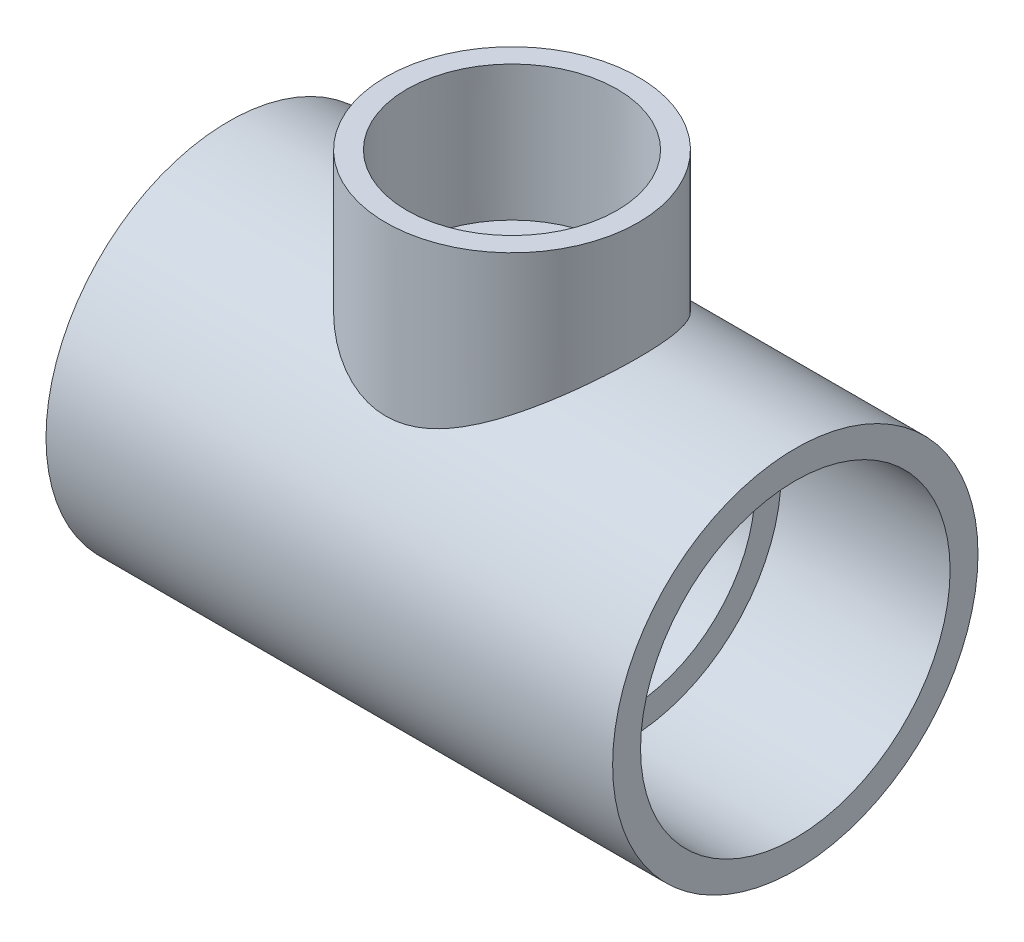
SolidWorks part; units mm, degrees
ref_plane "Front Plane" through (0, 0, 0) normal (0, 0, 1) x (1, 0, 0)
ref_plane "Top Plane" through (0, 0, 0) normal (0, 1, 0) x (1, 0, 0)
ref_plane "Right Plane" through (0, 0, 0) normal (1, 0, 0) x (0, 0, -1)
sketch "Sketch0" plane through (0, 0, 0) normal (0, 0, 1) x (1, 0, 0)
  line L0 (-81.7372, 0) -> (0, 0) construction
  line L1 (0, 0) -> (0, 86.4616) construction
  line L2 (-33.2994, 0) -> (0, 0) construction
  line L3 (0, 0) -> (0, 47.625) construction
  line L4 (-81.7372, 52.705) -> (-81.7372, -52.705) construction
  line L5 (-33.2994, 44.3484) -> (-81.7372, 44.6532) construction
  line L6 (-33.2994, 44.3484) -> (-33.2994, -44.3484) construction
  line L7 (-33.2994, -44.3484) -> (-81.7372, -44.6532) construction
  line L8 (-81.7372, 44.6532) -> (-81.7372, -44.6532) construction
  line L9 (-36.4109, 86.4616) -> (36.4109, 86.4616) construction
  line L10 (-30.3149, 86.4616) -> (30.3149, 86.4616) construction
  line L11 (30.3149, 86.4616) -> (30.0863, 47.625) construction
  line L12 (30.0863, 47.625) -> (-30.0863, 47.625) construction
  line L13 (-30.0863, 47.625) -> (-30.3149, 86.4616) construction
  line L14 (-33.2994, 36.83) -> (-33.2994, -36.83) construction
  line L15 (-81.7372, 0) -> (-33.2994, 0) construction
  line L16 (0, 86.4616) -> (0, 47.625) construction
  line L17 (0, 0) -> (33.2994, 0) construction
  line L18 (-24.6253, 47.625) -> (24.6253, 47.625) construction
  line L19 (33.2994, 0) -> (81.7372, 0) construction
  dimension "H" = 81.7372
  dimension "G" = 33.2994
  dimension "M" = 105.41
  dimension "OD A" = 89.3064
  dimension "OD B" = 88.6968
  dimension "ID" = 73.66
  dimension "H3" = 86.4616
  dimension "G3" = 47.625
  dimension "M3" = 72.8218
  dimension "OD A3" = 60.6298
  dimension "OD B3" = 60.1726
  dimension "ID3" = 49.2506
sketch "Sketch1" plane through (0, 0, 0) normal (0, 0, 1) x (1, 0, 0)
  line L0 (-81.7372, 0) -> (0, 0) construction
  line L1 (-81.7372, 0) -> (0, 0) construction
  line L2 (0, 0) -> (0, -52.705) construction
  line L3 (-81.7372, -52.705) -> (-33.2994, -52.705)
  line L4 (-81.7372, -52.705) -> (-81.7372, -44.6532)
  line L5 (-81.7372, -44.6532) -> (-33.2994, -44.3484)
  line L6 (-33.2994, -52.705) -> (-33.2994, -44.3484)
  line L7 (-33.2994, -52.705) -> (0, -52.705) construction
  line L8 (81.7372, -44.6532) -> (33.2994, -44.3484)
  line L9 (81.7372, -52.705) -> (81.7372, -44.6532)
  line L10 (33.2994, -52.705) -> (33.2994, -44.3484)
  line L11 (81.7372, -52.705) -> (33.2994, -52.705)
revolve "Revolve1" add sketch "Sketch1" angle 360 about L1
sketch "Sketch2" plane through (0, 0, 0) normal (0, 0, 1) x (1, 0, 0)
  line L0 (30.3149, 86.4616) -> (30.0863, 47.625)
  line L1 (30.0863, 47.625) -> (36.4109, 47.625)
  line L2 (36.4109, 47.625) -> (36.4109, 86.4616)
  line L3 (36.4109, 86.4616) -> (30.3149, 86.4616)
  line L4 (0, 0) -> (0, 86.4616) construction
  line L5 (0, 0) -> (0, 86.4616) construction
revolve "Revolve2" add sketch "Sketch2" angle 360 about L5
sketch "Sketch3" plane through (-33.2994, 0, 0) normal (1, 0, 0) x (0, 0, -1)
  circle A0 centre (0, 0) radius 36.83
  circle A1 centre (0, 0) radius 52.705
sketch "Sketch4" plane through (-33.2994, 0, 0) normal (1, 0, 0) x (0, 0, -1)
  circle A0 centre (0, 0) radius 52.705 construction
  circle A1 centre (0, 0) radius 52.705
extrude "Boss-Extrude1" add sketch "Sketch4" along normal up to vertex (66.5988 mm away) up to point (33.2994, 0, 0)
sketch "Sketch5" plane through (0, 47.625, 0) normal (0, -1, 0) x (1, 0, 0)
  circle A0 centre (0, 0) radius 36.4109 construction
  circle A1 centre (0, 0) radius 36.4109
extrude "Boss-Extrude2" add sketch "Sketch5" along normal up to vertex (47.625 mm away) up to point (0, 0, 0)
sketch "Sketch6" plane through (0, 0, 0) normal (0, 0, 1) x (1, 0, 0)
  line L0 (-81.7372, -44.6532) -> (-33.2994, -44.3484)
  line L1 (-33.2994, -44.3484) -> (-33.2994, -36.83)
  line L2 (-33.2994, -36.83) -> (33.2994, -36.83)
  line L3 (33.2994, -44.3484) -> (33.2994, 41.8315) construction
  line L4 (0, -36.83) -> (0, 0) construction
  line L5 (33.2994, -44.3484) -> (33.2994, -36.83)
  line L6 (81.7372, -44.6532) -> (81.7372, 44.6532) construction
  line L7 (81.7372, -52.705) -> (81.7372, 52.705) construction
  line L8 (81.7372, -44.6532) -> (81.7372, 0)
  line L9 (81.7372, 0) -> (-81.7372, 0)
  line L10 (-81.7372, 0) -> (-81.7372, -44.6532)
  line L11 (81.7372, -44.6532) -> (33.2994, -44.3484)
revolve "Cut-Revolve1" cut sketch "Sketch6" angle 360 about L9
sketch "Sketch7" plane through (0, 0, 0) normal (0, 0, 1) x (1, 0, 0)
  line L0 (30.3149, 86.4616) -> (30.0863, 47.625)
  line L1 (30.0863, 47.625) -> (24.6253, 47.625)
  line L2 (24.6253, 47.625) -> (24.6253, 0)
  line L3 (0, 0) -> (33.2994, 0) construction
  line L4 (24.6253, 0) -> (0, 0)
  line L5 (0, 0) -> (0, 86.4616)
  line L6 (-36.4109, 86.4616) -> (36.4109, 86.4616) construction
  line L7 (0, 86.4616) -> (30.3149, 86.4616)
revolve "Cut-Revolve2" cut sketch "Sketch7" angle 360 about L5
other "CPoint1" parameters "Diameter"=76.2, "StubLength"=76.2
ref_axis "Axis1" through (-43.2994, 0, 0) along (1, 0, 0)
other "CPoint2" parameters "Diameter"=76.2, "StubLength"=76.2
ref_axis "Axis2" through (43.2994, 0, 0) along (-1, 0, 0)
other "CPoint3" parameters "Diameter"=50.8, "StubLength"=76.2
ref_axis "Axis3" through (0, 57.625, 0) along (0, -1, 0)
other "RPoint1"
